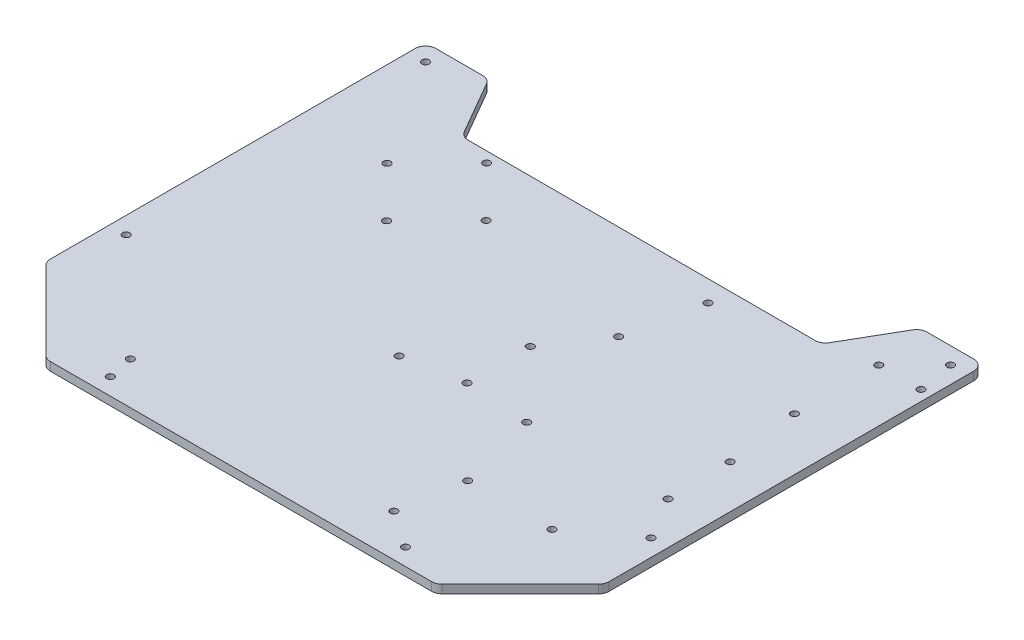
SolidWorks part; units mm, degrees
material "Acier non allié"
ref_plane "Front" through (0, 0, 0) normal (0, 0, 1) x (1, 0, 0)
ref_plane "Top" through (0, 0, 0) normal (0, 1, 0) x (1, 0, 0)
ref_plane "Right" through (0, 0, 0) normal (1, 0, 0) x (0, 0, -1)
sketch "Main scetch" plane through (0, 0, 0) normal (0, 1, 0) x (1, 0, 0)
  line L1 (0, 0) -> (132.5, 0) construction
  line L2 (0, 0) -> (0, 220) construction
  line L3 (0, 220) -> (132.5, 220) construction
  line L4 (132.5, 0) -> (132.5, 220) construction
  line L13 (-92.5, 0) -> (92.5, 0)
  line L14 (92.5, 0) -> (132.5, 40)
  line L15 (132.5, 40) -> (132.5, 220)
  line L16 (132.5, 220) -> (102.5, 220)
  line L17 (102.5, 220) -> (85.1795, 190)
  line L18 (85.1795, 190) -> (-85.1795, 190)
  line L19 (-102.5, 220) -> (-85.1795, 190)
  line L20 (-132.5, 220) -> (-102.5, 220)
  line L21 (-132.5, 40) -> (-132.5, 220)
  line L22 (-92.5, 0) -> (-132.5, 40)
  point P11 (0, 190)
  dimension "132.5" = 132.5
  dimension "D2" = 220
  dimension "D1" = 40
  dimension "D3" = 40
  dimension "D4" = 30
  dimension "D5" = 60
  dimension "D6" = 30
extrude "Main extrusion" add sketch "Main scetch" along normal blind 4
fillet "Congé1" radius 5 10 edges at (-132.5, 2, -40) (-92.5, 2, 0) (92.5, 2, 0) (132.5, 2, -40) (132.5, 2, -220) (102.5, 2, -220) (85.1795, 2, -190) (-85.1795, 2, -190) (-102.5, 2, -220) (-132.5, 2, -220)
sketch "Esquisse1" plane through (0, 4, 0) normal (0, 1, 0) x (1, 0, 0)
  line L0 (0, 0) -> (0, 218.5516) construction
  line L1 (132.5, 42.0711) -> (132.5, 215) construction
  line L2 (127.5, 220) -> (105.3868, 220) construction
  line L3 (-90.4289, 0) -> (90.4289, 0) construction
  circle A0 centre (70, 8) radius 1
  circle A1 centre (124.5, 70) radius 1
  circle A2 centre (124.5, 212) radius 1
  circle A3 centre (-124.5, 212) radius 1
  circle A4 centre (-124.5, 70) radius 1
  circle A5 centre (-70, 8) radius 1
  dimension "D1" = 2
  dimension "D2" = 2
  dimension "D3" = 2
  dimension "D4" = 8
  dimension "D5" = 8
  dimension "D6" = 8
  dimension "D7" = 8
  dimension "D8" = 70
  dimension "D9" = 70
extrude "Enlèv. mat.-Extru.1" cut sketch "Esquisse1" against normal through all
hole_wizard "Dégagement M31" positions "Esquisse2" profile "Esquisse3" hole size "M3" standard "ISO" end condition through all
sketch "Esquisse2" plane through (0, 4, 0) normal (0, 1, 0) x (1, 0, 0)
  point P0 (-124.5, 212)
  point P3 (-124.5, 70)
  point P6 (-70, 8)
  point P9 (70, 8)
  point P12 (124.5, 70)
  point P15 (124.5, 212)
sketch "Esquisse3" plane through (-124.5, 4, -212) normal (1, 0, 0) x (0, 0, 1)
  line L0 (0, 0) -> (0, 4)
  line L1 (0, 4) -> (1.7, 4)
  line L2 (1.7, 4) -> (1.7, 0)
  line L5 (1.7, 0) -> (0, 0)
  line L11 (0, -6.35) -> (0, 107.95) construction
  dimension "Diamètre du perçage jusqu'au prochain" = 3.4
  dimension "Profondeur du perçage jusqu'au prochain" = 4
sketch "Esquisse4" plane through (0, 4, 0) normal (0, 1, 0) x (1, 0, 0)
  line L0 (-132.5, 215) -> (-132.5, 42.0711) construction
  line L2 (82.2927, 190) -> (-82.2927, 190) construction
  line L3 (132.5, 42.0711) -> (132.5, 215) construction
  line L4 (-90.4289, 0) -> (90.4289, 0) construction
  line L5 (127.5, 220) -> (105.3868, 220) construction
  circle A1 centre (-68.5, 185) radius 1
  circle A5 centre (41.5, 180) radius 1
  circle A6 centre (34.12, 145) radius 1
  circle A7 centre (107.5, 155) radius 1
  circle A8 centre (127.5, 195) radius 1
  circle A9 centre (112, 120) radius 1
  circle A10 centre (112.5, 90) radius 1
  circle A11 centre (17.2, 120) radius 1
  circle A12 centre (17.2, 90) radius 1
  circle A13 centre (47.5, 88) radius 1
  circle A14 centre (57.5, 50) radius 1
  circle A15 centre (97.5, 50) radius 1
  circle A16 centre (52.5, 20) radius 1
  circle A17 centre (-10, 85) radius 1
  circle A18 centre (-72.5, 20) radius 1
  circle A19 centre (107.5, 195) radius 1
  circle A20 centre (-68.5, 137.5) radius 1
  circle A21 centre (-92, 161.25) radius 1
  circle A22 centre (-45, 161.25) radius 1
  dimension "D4" = 2
  dimension "D13" = 2
  dimension "D16" = 2
  dimension "D19" = 2
  dimension "D24" = 2
  dimension "D25" = 2
  dimension "D28" = 2
  dimension "D30" = 2
  dimension "D32" = 2
  dimension "D36" = 2
  dimension "D37" = 2
  dimension "D40" = 2
  dimension "D48" = 2
  dimension "D49" = 2
  dimension "D50" = 2
  dimension "D52" = 2
  dimension "D57" = 2
  dimension "D63" = 2
  dimension "D64" = 2
  dimension "D14" = 174
  dimension "D15" = 10
  dimension "D17" = 166.62
  dimension "D18" = 45
  dimension "D20" = 25
  dimension "D21" = 65
  dimension "D22" = 5
  dimension "D23" = 25
  dimension "D26" = 20.5
  dimension "D27" = 100
  dimension "D29" = 30
  dimension "D31" = 115.3
  dimension "D33" = 115.3
  dimension "D34" = 132
  dimension "D35" = 85
  dimension "D38" = 50
  dimension "D39" = 75
  dimension "D41" = 35
  dimension "D42" = 80
  dimension "D43" = 20
  dimension "D44" = 20
  dimension "D45" = 205
  dimension "D46" = 85
  dimension "D47" = 142.5
  dimension "D51" = 25
  dimension "D53" = 25
  dimension "D54" = 5
  dimension "D55" = 64
  dimension "D56" = 47.5
  dimension "D58" = 64
  dimension "D59" = 28.75
  dimension "D60" = 40.5
  dimension "D61" = 47
  dimension "D62" = 28.75
extrude "Enlèv. mat.-Extru.2" cut sketch "Esquisse4" against normal through all
hole_wizard "Dégagement M32" positions "Esquisse5" profile "Esquisse6" hole size "M3" standard "ISO" end condition through all
sketch "Esquisse5" plane through (0, 4, 0) normal (0, 1, 0) x (1, 0, 0)
  point P0 (-68.5, 185)
  point P9 (17.2, 120)
  point P18 (34.12, 145)
  point P21 (41.5, 180)
  point P24 (107.5, 155)
  point P27 (127.5, 195)
  point P30 (112, 120)
  point P33 (112.5, 90)
  point P36 (47.5, 88)
  point P39 (17.2, 90)
  point P42 (57.5, 50)
  point P45 (97.5, 50)
  point P48 (-10, 85)
  point P51 (-72.5, 20)
  point P54 (52.5, 20)
  point P57 (107.5, 195)
  point P72 (-68.5, 137.5)
  point P76 (-92, 161.25)
  point P79 (-45, 161.25)
  point P82 (0, 0)
  point P83 (0, 0)
  point P84 (0, 0)
  point P85 (0, 0)
sketch "Esquisse6" plane through (-68.5, 4, -185) normal (1, 0, 0) x (0, 0, 1)
  line L0 (0, 0) -> (0, 4)
  line L1 (0, 4) -> (1.7, 4)
  line L2 (1.7, 4) -> (1.7, 0)
  line L5 (1.7, 0) -> (0, 0)
  line L11 (0, -6.35) -> (0, 107.95) construction
  dimension "Diamètre du perçage jusqu'au prochain" = 3.4
  dimension "Profondeur du perçage jusqu'au prochain" = 4
equation "\"WIDTH\"= 300mm'Total width of the robot"
equation "\"LENGTH\"= 220mm'Total length of the robot"
equation "\"D2@Main scetch\" = \"LENGTH\""
equation "\"CUT_DEPTH\"= 45mm'Depth of the cut on the edges of the plate"
equation "\"Plate_th\"= 3mm'Thickness of the plate"
equation "\"D1\"= \"Plate_th\""
equation "\"D47@Esquisse4\"=(80+205)/2"
